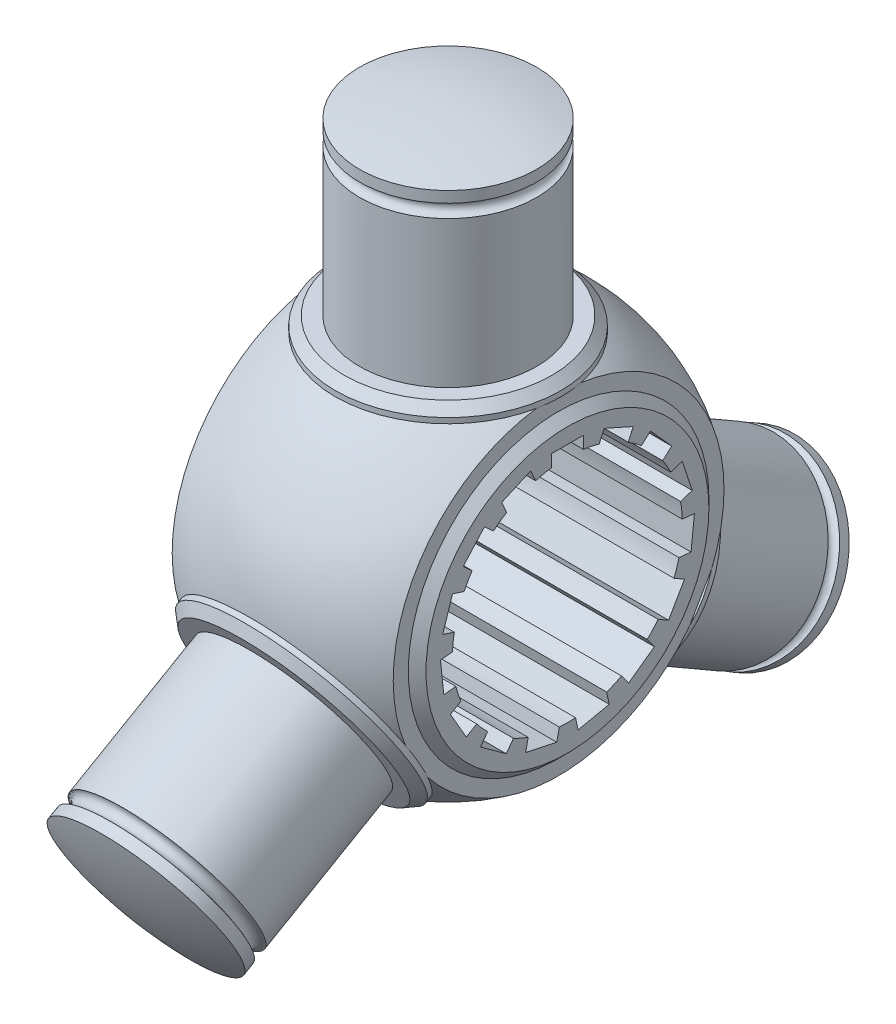
SolidWorks part; units mm, degrees
material "Cast Carbon Steel"
ref_plane "Front Plane" through (0, 0, 0) normal (0, 0, 1) x (1, 0, 0)
ref_plane "Top Plane" through (0, 0, 0) normal (0, 1, 0) x (1, 0, 0)
ref_plane "Right Plane" through (0, 0, 0) normal (1, 0, 0) x (0, 0, -1)
sketch "Sketch1" plane through (0, 0, 0) normal (0, 0, 1) x (1, 0, 0)
  line L0 (0, 13) -> (0, 22.5) construction
  line L1 (12.5, 13) -> (12.5, 18.7083)
  line L2 (-12.5, 13) -> (-12.5, 18.7083)
  line L3 (-12.5, 13) -> (12.5, 13)
  line L4 (0, 0) -> (47.1351, 0) construction
  line L5 (-12.5, 0) -> (-12.5, 27.9896) construction
  line L6 (0, 0) -> (0, 27.9896) construction
  line L7 (12.5, 0) -> (12.5, 27.9896) construction
  arc A0 (12.5, 18.7083) -> (-12.5, 18.7083) centre (0, 0) ccw
  dimension "D1" = 45
  dimension "D4" = 13
  dimension "D2" = 12.5
  dimension "D3" = 12.5
revolve "Revolve1" add sketch "Sketch1" angle 360 about L4
sketch "Sketch2" plane through (12.5, 0, 0) normal (1, 0, 0) x (0, 0, -1)
  circle A0 centre (0, 0) radius 13 construction
  circle A1 centre (0, 0) radius 18.7083
  circle A2 centre (0, 0) radius 18.7083
  circle A3 centre (0, 0) radius 13
  dimension "D1" = 0
sketch "Sketch3" plane through (12.5, 0, 0) normal (1, 0, 0) x (0, 0, -1)
  circle A0 centre (0, 0) radius 13 construction
  circle A1 centre (0, 0) radius 13
  circle A2 centre (0, 0) radius 17
  dimension "D1" = 4
extrude "Boss-Extrude1" add sketch "Sketch3" along normal blind 1
chamfer "Chamfer1" distance 1 angle 45 1 edges at (13.5, 0, -17)
sketch "Sketch7" plane through (0, 0, 0) normal (1, 0, 0) x (0, 0, -1)
  line L0 (0, 18.7083) -> (0, 40.7083)
  line L1 (10.0192, 39.4561) -> (10.0192, 20.1461)
  line L2 (10.0192, 20.1461) -> (12.75, 20.1461)
  line L3 (12.75, 20.1461) -> (12.75, 18.5388)
  line L4 (12.75, 18.5388) -> (0, 18.7083)
  circle A0 centre (0, 0) radius 18.7083 construction
  arc A1 (0, 40.7083) -> (10.0192, 39.4561) centre (0, -0.0017) cw
  circle A2 centre (0, 0) radius 22.5 construction
  dimension "D4" = 40.71
  dimension "D1" = 22
  dimension "D2" = 19.31
  dimension "D3" = 12.75
revolve "Revolve2" add sketch "Sketch7" angle 360 about L0
chamfer "Chamfer2" distance 1 angle 45 1 edges at (0, 20.1461, -12.75)
sketch "Sketch8" plane through (0, 0, 0) normal (1, 0, 0) x (0, 0, -1)
  line L0 (10.0192, 20.1461) -> (10.0192, 39.4561) construction
  line L1 (0, 20.1461) -> (0, 40.7083) construction
  line L2 (11.75, 20.1461) -> (-11.75, 20.1461) construction
  circle A0 centre (10.0192, 37.4561) radius 0.75
  arc A1 (10.0192, 39.4561) -> (-10.0192, 39.4561) centre (0, -0.0017) ccw construction
  dimension "D1" = 1.5
  dimension "D2" = 2
revolve "Cut-Revolve1" cut sketch "Sketch8" angle 360 about L1
pattern_circular "CirPattern2" count 3 over 360 about axis through (0, 0, 0) along (1, 0, 0) of "Revolve2", "Chamfer2", "Cut-Revolve1"
sketch "Sketch9" plane through (13.5, 0, 0) normal (1, 0, 0) x (0, 0, -1)
  line L0 (0, 0) -> (0, 14.25) construction
  line L1 (1.8, 14.25) -> (-1.8, 14.25)
  line L2 (-1.8, 14.25) -> (-1.8, 12.25)
  line L3 (-1.8, 12.25) -> (1.8, 12.25)
  line L4 (1.8, 14.25) -> (1.8, 12.25)
  point P7 (0, 12.25)
  dimension "D1" = 14.25
  dimension "D2" = 1.8
  dimension "D3" = 2
extrude "Cut-Extrude1" cut sketch "Sketch9" against normal through all
pattern_circular "CirPattern3" count 15 over 360 about axis through (0, 0, 0) along (1, 0, 0) of "Cut-Extrude1"
